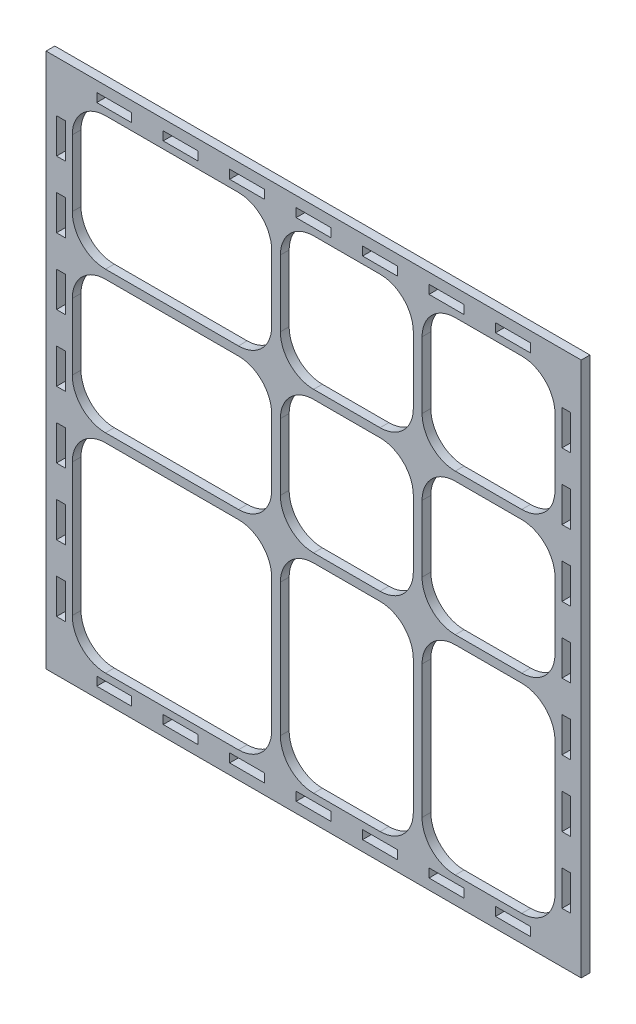
SolidWorks part; units mm, degrees
material "Beech"
ref_plane "Front" through (0, 0, 0) normal (0, 0, 1) x (1, 0, 0)
ref_plane "Top" through (0, 0, 0) normal (0, 1, 0) x (1, 0, 0)
ref_plane "Right" through (0, 0, 0) normal (1, 0, 0) x (0, 0, -1)
sketch "Sketch1" plane through (0, 0, 0) normal (0, 0, 1) x (1, 0, 0)
  line L0 (0, 14.1468) -> (0, -17.5978) construction
  line L1 (-76.5, -76.5) -> (76.5, -76.5)
  line L2 (-76.5, -76.5) -> (-76.5, 76.5)
  line L3 (-76.5, 76.5) -> (76.5, 76.5)
  line L4 (76.5, -76.5) -> (76.5, 76.5)
  line L5 (-76.5, -76.5) -> (76.5, 76.5) construction
  line L6 (-76.5, 76.5) -> (76.5, -76.5) construction
  line L7 (-73.5, 52) -> (-71, 52)
  line L8 (-73.5, 52) -> (-73.5, 62)
  line L9 (-73.5, 62) -> (-71, 62)
  line L10 (-71, 52) -> (-71, 62)
  line L11 (-73.5, 52) -> (-71, 62) construction
  line L12 (-73.5, 62) -> (-71, 52) construction
  line L13 (-21.7287, 0) -> (19.2748, 0) construction
  line L14 (-73.5, 33) -> (-73.5, 43)
  line L15 (-73.5, 33) -> (-71, 33)
  line L16 (-71, 33) -> (-71, 43)
  line L17 (-73.5, 43) -> (-71, 43)
  line L18 (-73.5, 14) -> (-73.5, 24)
  line L19 (-73.5, 14) -> (-71, 14)
  line L20 (-71, 14) -> (-71, 24)
  line L21 (-73.5, 24) -> (-71, 24)
  line L22 (-73.5, -5) -> (-73.5, 5)
  line L23 (-73.5, -5) -> (-71, -5)
  line L24 (-71, -5) -> (-71, 5)
  line L25 (-73.5, 5) -> (-71, 5)
  line L26 (-73.5, -24) -> (-73.5, -14)
  line L27 (-73.5, -24) -> (-71, -24)
  line L28 (-71, -24) -> (-71, -14)
  line L29 (-73.5, -14) -> (-71, -14)
  line L30 (-73.5, -43) -> (-73.5, -33)
  line L31 (-73.5, -43) -> (-71, -43)
  line L32 (-71, -43) -> (-71, -33)
  line L33 (-73.5, -33) -> (-71, -33)
  line L34 (-73.5, -62) -> (-73.5, -52)
  line L35 (-73.5, -62) -> (-71, -62)
  line L36 (-71, -62) -> (-71, -52)
  line L37 (-73.5, -52) -> (-71, -52)
  line L70 (73.5, -24) -> (71, -24)
  line L71 (71, -24) -> (71, -14)
  line L72 (73.5, -14) -> (71, -14)
  line L73 (73.5, -24) -> (73.5, -14)
  line L74 (73.5, -43) -> (71, -43)
  line L75 (71, -43) -> (71, -33)
  line L76 (73.5, -33) -> (71, -33)
  line L77 (73.5, -43) -> (73.5, -33)
  line L78 (73.5, -62) -> (71, -62)
  line L79 (71, -62) -> (71, -52)
  line L80 (73.5, -52) -> (71, -52)
  line L81 (73.5, -62) -> (73.5, -52)
  line L82 (73.5, -5) -> (71, -5)
  line L83 (71, -5) -> (71, 5)
  line L84 (73.5, 5) -> (71, 5)
  line L85 (73.5, -5) -> (73.5, 5)
  line L86 (73.5, 14) -> (71, 14)
  line L87 (71, 14) -> (71, 24)
  line L88 (73.5, 24) -> (71, 24)
  line L89 (73.5, 14) -> (73.5, 24)
  line L90 (73.5, 33) -> (71, 33)
  line L91 (71, 33) -> (71, 43)
  line L92 (73.5, 43) -> (71, 43)
  line L93 (73.5, 33) -> (73.5, 43)
  line L94 (73.5, 62) -> (71, 62)
  line L95 (71, 52) -> (71, 62)
  line L96 (73.5, 52) -> (71, 52)
  line L97 (73.5, 52) -> (73.5, 62)
  line L98 (-62, -73.5) -> (-52, -73.5)
  line L99 (-62, 71) -> (-52, 71)
  line L100 (-62, 71) -> (-62, 73.5)
  line L101 (-62, 73.5) -> (-52, 73.5)
  line L102 (-52, 71) -> (-52, 73.5)
  line L103 (-62, 71) -> (-52, 73.5) construction
  line L104 (-62, 73.5) -> (-52, 71) construction
  line L105 (-52, -71) -> (-52, -73.5)
  line L106 (-62, -71) -> (-52, -71)
  line L107 (-62, -71) -> (-62, -73.5)
  line L108 (-43, 71) -> (-43, 73.5)
  line L109 (-43, 71) -> (-33, 71)
  line L110 (-33, 71) -> (-33, 73.5)
  line L111 (-43, 73.5) -> (-33, 73.5)
  line L112 (-43, -73.5) -> (-33, -73.5)
  line L113 (-33, -71) -> (-33, -73.5)
  line L114 (-43, -71) -> (-33, -71)
  line L115 (-43, -71) -> (-43, -73.5)
  line L116 (-24, 71) -> (-24, 73.5)
  line L117 (-24, 71) -> (-14, 71)
  line L118 (-14, 71) -> (-14, 73.5)
  line L119 (-24, 73.5) -> (-14, 73.5)
  line L120 (-24, -73.5) -> (-14, -73.5)
  line L121 (-14, -71) -> (-14, -73.5)
  line L122 (-24, -71) -> (-14, -71)
  line L123 (-24, -71) -> (-24, -73.5)
  line L124 (-5, 71) -> (-5, 73.5)
  line L125 (-5, 71) -> (5, 71)
  line L126 (5, 71) -> (5, 73.5)
  line L127 (-5, 73.5) -> (5, 73.5)
  line L128 (-5, -73.5) -> (5, -73.5)
  line L129 (5, -71) -> (5, -73.5)
  line L130 (-5, -71) -> (5, -71)
  line L131 (-5, -71) -> (-5, -73.5)
  line L132 (14, 71) -> (14, 73.5)
  line L133 (14, 71) -> (24, 71)
  line L134 (24, 71) -> (24, 73.5)
  line L135 (14, 73.5) -> (24, 73.5)
  line L136 (14, -73.5) -> (24, -73.5)
  line L137 (24, -71) -> (24, -73.5)
  line L138 (14, -71) -> (24, -71)
  line L139 (14, -71) -> (14, -73.5)
  line L140 (33, 71) -> (33, 73.5)
  line L141 (33, 71) -> (43, 71)
  line L142 (43, 71) -> (43, 73.5)
  line L143 (33, 73.5) -> (43, 73.5)
  line L144 (33, -73.5) -> (43, -73.5)
  line L145 (43, -71) -> (43, -73.5)
  line L146 (33, -71) -> (43, -71)
  line L147 (33, -71) -> (33, -73.5)
  line L148 (52, 71) -> (52, 73.5)
  line L149 (52, 71) -> (62, 71)
  line L150 (62, 71) -> (62, 73.5)
  line L151 (52, 73.5) -> (62, 73.5)
  line L152 (52, -73.5) -> (62, -73.5)
  line L153 (62, -71) -> (62, -73.5)
  line L154 (52, -71) -> (62, -71)
  line L155 (52, -71) -> (52, -73.5)
  line L156 (54.5328, 69) -> (69, 69) construction
  line L157 (69, 69) -> (69, 53.5325) construction
  line L158 (-9.5031, 59.4969) -> (-9.5031, 40.4969)
  line L159 (40.5, 69) -> (59.5, 69)
  line L160 (31, 59.5) -> (31, 40.5)
  line L161 (40.5, 31) -> (59.5, 31)
  line L162 (69, 59.5) -> (69, 40.5)
  line L163 (-0.0031, 68.9969) -> (18.9969, 68.9969)
  line L164 (28.4969, 59.4969) -> (28.4969, 40.4969)
  line L165 (-0.0031, 30.9969) -> (18.9969, 30.9969)
  line L166 (-9.5031, 18.9969) -> (-9.5031, -0.0031)
  line L167 (-0.0031, 28.4969) -> (18.9969, 28.4969)
  line L168 (28.4969, 18.9969) -> (28.4969, -0.0031)
  line L169 (-0.0031, -9.5031) -> (18.9969, -9.5031)
  line L170 (31, 18.9969) -> (31, -0.0031)
  line L171 (40.5, 28.4969) -> (59.5, 28.4969)
  line L172 (69, 18.9969) -> (69, -0.0031)
  line L173 (40.5, -9.5031) -> (59.5, -9.5031)
  line L174 (-69.0031, 18.9969) -> (-69.0031, -0.0031)
  line L175 (-59.5031, 68.9969) -> (-21.5031, 68.9969)
  line L176 (-69.0031, 59.4969) -> (-69.0031, 40.4969)
  line L177 (-59.5031, 30.9969) -> (-21.5031, 30.9969)
  line L178 (-12.0031, 59.4969) -> (-12.0031, 40.4969)
  line L179 (-59.5031, 28.4969) -> (-21.5031, 28.4969)
  line L180 (-12.0031, 18.9969) -> (-12.0031, -0.0031)
  line L181 (-59.5031, -9.5031) -> (-21.5031, -9.5031)
  line L182 (-9.5031, -21.5031) -> (-9.5031, -59.5031)
  line L183 (40.4969, -12.0031) -> (59.4969, -12.0031)
  line L184 (30.9969, -21.5031) -> (30.9969, -59.5031)
  line L185 (40.4969, -69.0031) -> (59.4969, -69.0031)
  line L186 (68.9969, -21.5031) -> (68.9969, -59.5031)
  line L187 (-0.0031, -12.0031) -> (18.9969, -12.0031)
  line L188 (28.4969, -21.5031) -> (28.4969, -59.5031)
  line L189 (-0.0031, -69.0031) -> (18.9969, -69.0031)
  line L190 (-59.5031, -12.0031) -> (-21.5031, -12.0031)
  line L191 (-69.0031, -21.5031) -> (-69.0031, -59.5031)
  line L192 (-59.5031, -69.0031) -> (-21.5031, -69.0031)
  line L193 (-12.0031, -21.5031) -> (-12.0031, -59.5031)
  arc A0 (59.5, 69) -> (69, 59.5) centre (59.5, 59.5) cw
  arc A1 (59.5, 31) -> (69, 40.5) centre (59.5, 40.5) ccw
  arc A2 (31, 40.5) -> (40.5, 31) centre (40.5, 40.5) ccw
  arc A3 (40.5, 69) -> (31, 59.5) centre (40.5, 59.5) ccw
  arc A4 (-0.0031, 68.9969) -> (-9.5031, 59.4969) centre (-0.0031, 59.4969) ccw
  arc A5 (-9.5031, 40.4969) -> (-0.0031, 30.9969) centre (-0.0031, 40.4969) ccw
  arc A6 (18.9969, 68.9969) -> (28.4969, 59.4969) centre (18.9969, 59.4969) cw
  arc A7 (18.9969, 30.9969) -> (28.4969, 40.4969) centre (18.9969, 40.4969) ccw
  arc A8 (-0.0031, 28.4969) -> (-9.5031, 18.9969) centre (-0.0031, 18.9969) ccw
  arc A9 (-9.5031, -0.0031) -> (-0.0031, -9.5031) centre (-0.0031, -0.0031) ccw
  arc A10 (18.9969, 28.4969) -> (28.4969, 18.9969) centre (18.9969, 18.9969) cw
  arc A11 (18.9969, -9.5031) -> (28.4969, -0.0031) centre (18.9969, -0.0031) ccw
  arc A12 (40.5, 28.4969) -> (31, 18.9969) centre (40.5, 18.9969) ccw
  arc A13 (31, -0.0031) -> (40.5, -9.5031) centre (40.5, -0.0031) ccw
  arc A14 (59.5, 28.4969) -> (69, 18.9969) centre (59.5, 18.9969) cw
  arc A15 (59.5, -9.5031) -> (69, -0.0031) centre (59.5, -0.0031) ccw
  arc A16 (-21.5031, 30.9969) -> (-12.0031, 40.4969) centre (-21.5031, 40.4969) ccw
  arc A17 (-21.5031, 68.9969) -> (-12.0031, 59.4969) centre (-21.5031, 59.4969) cw
  arc A18 (-59.5031, 68.9969) -> (-69.0031, 59.4969) centre (-59.5031, 59.4969) ccw
  arc A19 (-69.0031, 40.4969) -> (-59.5031, 30.9969) centre (-59.5031, 40.4969) ccw
  arc A20 (-69.0031, -0.0031) -> (-59.5031, -9.5031) centre (-59.5031, -0.0031) ccw
  arc A21 (-59.5031, 28.4969) -> (-69.0031, 18.9969) centre (-59.5031, 18.9969) ccw
  arc A22 (-21.5031, 28.4969) -> (-12.0031, 18.9969) centre (-21.5031, 18.9969) cw
  arc A23 (-21.5031, -9.5031) -> (-12.0031, -0.0031) centre (-21.5031, -0.0031) ccw
  arc A24 (59.4969, -12.0031) -> (68.9969, -21.5031) centre (59.4969, -21.5031) cw
  arc A25 (59.4969, -69.0031) -> (68.9969, -59.5031) centre (59.4969, -59.5031) ccw
  arc A26 (30.9969, -59.5031) -> (40.4969, -69.0031) centre (40.4969, -59.5031) ccw
  arc A27 (40.4969, -12.0031) -> (30.9969, -21.5031) centre (40.4969, -21.5031) ccw
  arc A28 (-0.0031, -12.0031) -> (-9.5031, -21.5031) centre (-0.0031, -21.5031) ccw
  arc A29 (-9.5031, -59.5031) -> (-0.0031, -69.0031) centre (-0.0031, -59.5031) ccw
  arc A30 (18.9969, -12.0031) -> (28.4969, -21.5031) centre (18.9969, -21.5031) cw
  arc A31 (18.9969, -69.0031) -> (28.4969, -59.5031) centre (18.9969, -59.5031) ccw
  arc A32 (-21.5031, -69.0031) -> (-12.0031, -59.5031) centre (-21.5031, -59.5031) ccw
  arc A33 (-69.0031, -59.5031) -> (-59.5031, -69.0031) centre (-59.5031, -59.5031) ccw
  arc A34 (-59.5031, -12.0031) -> (-69.0031, -21.5031) centre (-59.5031, -21.5031) ccw
  arc A35 (-21.5031, -12.0031) -> (-12.0031, -21.5031) centre (-21.5031, -21.5031) cw
  point P0 (0, 0)
  point P6 (-72.25, 57)
  point P67 (-57, 72.25)
  dimension "D1" = 153
  dimension "D2" = 153
  dimension "D3" = 10
  dimension "D4" = 2.5
  dimension "D5" = 3
  dimension "D6" = 14.5
  dimension "D8" = 9
  dimension "D9" = 3
  dimension "D10" = 14.5
  dimension "D12" = 9
  dimension "D13" = 2
  dimension "D14" = 2
  dimension "D7" = 7
  dimension "D11" = 7
extrude "Boss-Extrude1" [suppressed] add sketch "Sketch1" along normal blind 2.5 contours L1 L4 L3 L2 L155 L154 L153 L152 L147 L146 L145 L144 L139 L138 L137 L136 L131 L130 L129 L128 L123 L122 L121 L120 L115 L114 L113 L112 L107 L106 L105 L98 L102 L99 L100 L101 L97 L96 L95 L94 L93 | L176 A19 L177 A16 L178 A17 L175 A18 | L165 A7 L164 A6 L163 A4 L158 A5 | L159 A3 L160 A2 L161 A1 L162 A0 | L173 A15 L172 A14 L171 A12 L170 A13 | L169 A11 L168 A10 L167 A8 L166 A9 | L181 A23 L180 A22 L179 A21 L174 A20 | A35 L190 A34 L191 A33 L192 A32 L193 | L189 A31 L188 A30 L187 A28 L182 A29 | L183 A27 L184 A26 L185 A25 L186 A24
fillet "Fillet1" [suppressed] radius 3
extrude "Boss-Extrude2" add sketch "Sketch1<3>" along normal blind 2.5 contours L1 L4 L3 L2 A31 L189 A29 L182 A28 L187 A30 L188 A27 L183 A24 L186 A25 L185 A26 L184 A23 L181 A20 L174 A21 L179 A22 L180 A19 L176 A18 L175 A17 L178 A16 L177 A15 L173 A13 L170 A12 L171 A14 L172 A11 region at (-74.3363, 0, 0)
sketch "Sketch1<3>" plane through (0, 0, 0) normal (0, 0, 1) x (1, 0, 0) same geometry as "Sketch1"
